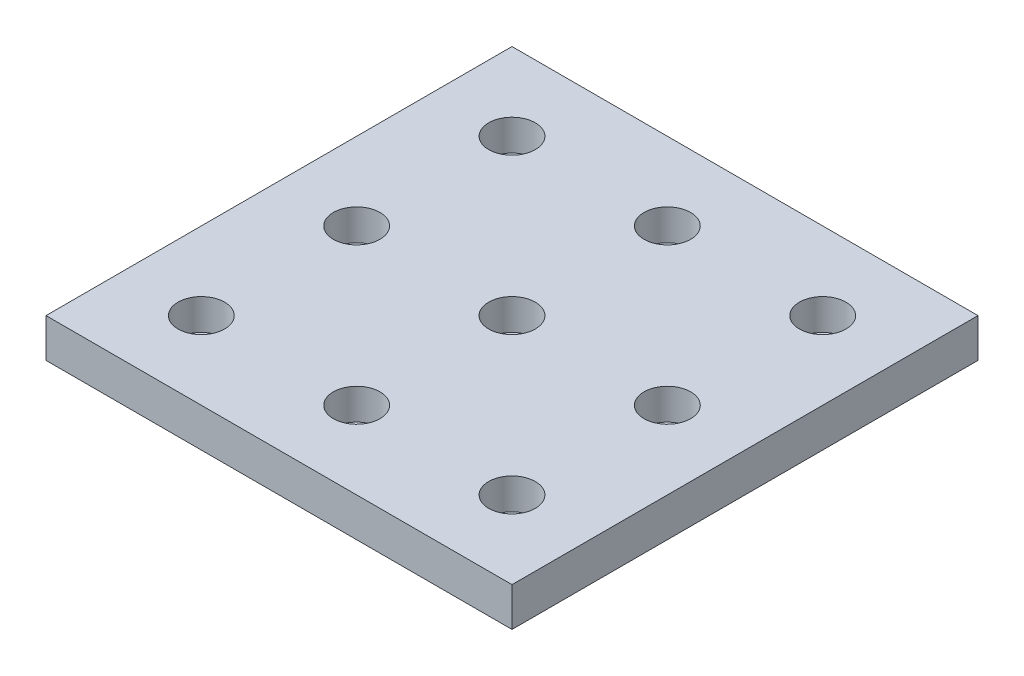
SolidWorks part; units mm, degrees
ref_plane "Front Plane" through (0, 0, 0) normal (0, 0, 1) x (1, 0, 0)
ref_plane "Top Plane" through (0, 0, 0) normal (0, 1, 0) x (1, 0, 0)
ref_plane "Right Plane" through (0, 0, 0) normal (1, 0, 0) x (0, 0, -1)
sketch "Sketch1" plane through (0, 0, 0) normal (0, 1, 0) x (1, 0, 0)
  line L1 (-52.9114, 51.2934) -> (7.0886, 51.2934)
  line L2 (-52.9114, 51.2934) -> (-52.9114, -8.7066)
  line L3 (-52.9114, -8.7066) -> (7.0886, -8.7066)
  line L4 (7.0886, 51.2934) -> (7.0886, -8.7066)
  circle A0 centre (-42.9114, 41.2934) radius 2.5
  circle A1 centre (-42.9114, 41.2934) radius 3
  circle A2 centre (-22.9114, 41.2934) radius 3
  circle A3 centre (-22.9114, 41.2934) radius 2.5
  circle A4 centre (-2.9114, 41.2934) radius 3
  circle A5 centre (-2.9114, 41.2934) radius 2.5
  circle A6 centre (-22.9114, 21.2934) radius 3
  circle A7 centre (-22.9114, 21.2934) radius 2.5
  circle A8 centre (-2.9114, 21.2934) radius 3
  circle A9 centre (-2.9114, 21.2934) radius 2.5
  circle A10 centre (-22.9114, 1.2934) radius 3
  circle A11 centre (-22.9114, 1.2934) radius 2.5
  circle A12 centre (-2.9114, 1.2934) radius 3
  circle A13 centre (-2.9114, 1.2934) radius 2.5
  circle A14 centre (-42.9114, 21.2934) radius 3
  circle A15 centre (-42.9114, 21.2934) radius 2.5
  circle A16 centre (-42.9114, 1.2934) radius 3
  circle A17 centre (-42.9114, 1.2934) radius 2.5
  dimension "D5" = 5
  dimension "D6" = 6
  dimension "D1" = 60
  dimension "D2" = 60
  dimension "D3" = 10
  dimension "D4" = 10
  dimension "D7" = 3
  dimension "D8" = 3
extrude "Boss-Extrude1" add sketch "Sketch1" along normal blind 5 contours L4 L1 L2 L3 A16 A14 A12 A10 A8 A6 A4 A2 A1 region at (-22.9114, 0, -50.4448)
extrude "Boss-Extrude2" add sketch "Sketch1<3>" along normal blind 1 contours A16 A17 | A10 A11 | A12 A13 | A8 A9 | A6 A7 | A14 A15 | A1 A0 | A2 A3 | A4 A5 region at (-45.8265, 0, -41.2934) region at (-25.8265, 0, -41.2934) region at (-5.8265, 0, -41.2934) region at (-25.8265, 0, -21.2934) region at (-5.8265, 0, -21.2934) region at (-25.8265, 0, -1.2934) region at (-5.8265, 0, -1.2934) region at (-45.8265, 0, -21.2934) region at (-45.8265, 0, -1.2934)
sketch "Sketch1<3>" plane through (0, 0, 0) normal (0, 1, 0) x (1, 0, 0) same geometry as "Sketch1"
